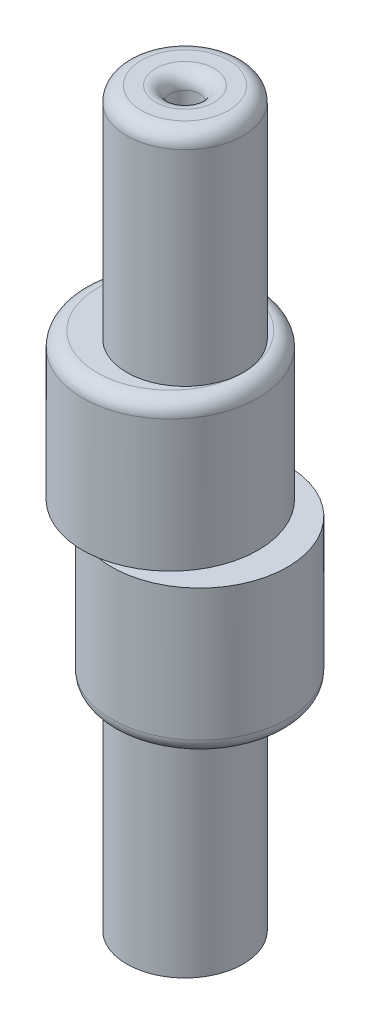
SolidWorks part; units mm, degrees
ref_plane "Front Plane" through (0, 0, 0) normal (0, 0, 1) x (1, 0, 0)
ref_plane "Top Plane" through (0, 0, 0) normal (0, 1, 0) x (1, 0, 0)
ref_plane "Right Plane" through (0, 0, 0) normal (1, 0, 0) x (0, 0, -1)
sketch "Sketch1" plane through (0, 0, 0) normal (0, 1, 0) x (1, 0, 0)
  circle A0 centre (0, 0) radius 3.975
  dimension "D1" = 7.95
extrude "Boss-Extrude1" add sketch "Sketch1" along normal blind 15
sketch "Sketch2" plane through (0, 15, 0) normal (0, 1, 0) x (1, 0, 0)
  line L0 (-4.5862, 0) -> (4.707, 0) construction
  circle A0 centre (1, 0) radius 6
  dimension "D2" = 12
  dimension "D1" = 1
extrude "Boss-Extrude2" add sketch "Sketch2" along normal blind 10
sketch "Sketch3" plane through (0, 25, 0) normal (0, 1, 0) x (1, 0, 0)
  line L0 (-7.6765, 0) -> (8.136, 0) construction
  circle A0 centre (-1, 0) radius 6
  dimension "D2" = 12
  dimension "D1" = 1
extrude "Boss-Extrude3" add sketch "Sketch3" along normal blind 10
sketch "Sketch4" plane through (0, 35, 0) normal (0, 1, 0) x (1, 0, 0)
  circle A0 centre (0, 0) radius 3.975
  dimension "D1" = 7.95
extrude "Boss-Extrude4" add sketch "Sketch4" along normal blind 15
sketch "Sketch5" plane through (0, 0, 0) normal (0, -1, 0) x (1, 0, 0)
  line L0 (0, -2.65) -> (-2.1974, -2.65) construction
  line L1 (-2.1974, -2.65) -> (2.7864, -2.65) construction
  line L2 (-1.5492, 2.15) -> (1.5492, 2.15)
  arc A0 (-1.5492, 2.15) -> (1.5492, 2.15) centre (0, 0) ccw
  dimension "D1" = 5.3
  dimension "D2" = 4.8
extrude "Cut-Extrude1" cut sketch "Sketch5" against normal blind 35.1
sketch "Sketch6" plane through (0, 50, 0) normal (0, 1, 0) x (1, 0, 0)
  circle A0 centre (0, 0) radius 1
extrude "Cut-Extrude2" cut sketch "Sketch6" against normal blind 45
fillet "Fillet1" radius 1 4 edges at (1, 15, 6) (-1, 35, 6) (0, 50, 3.975) (0, 50, 1)
fillet "Fillet2" radius 1 2 edges at (0, 0, 2.15) (0, 0, -2.65)
chamfer "Chamfer1" distance 1 angle 45 1 edges at (0, 35.1, -2.65)
